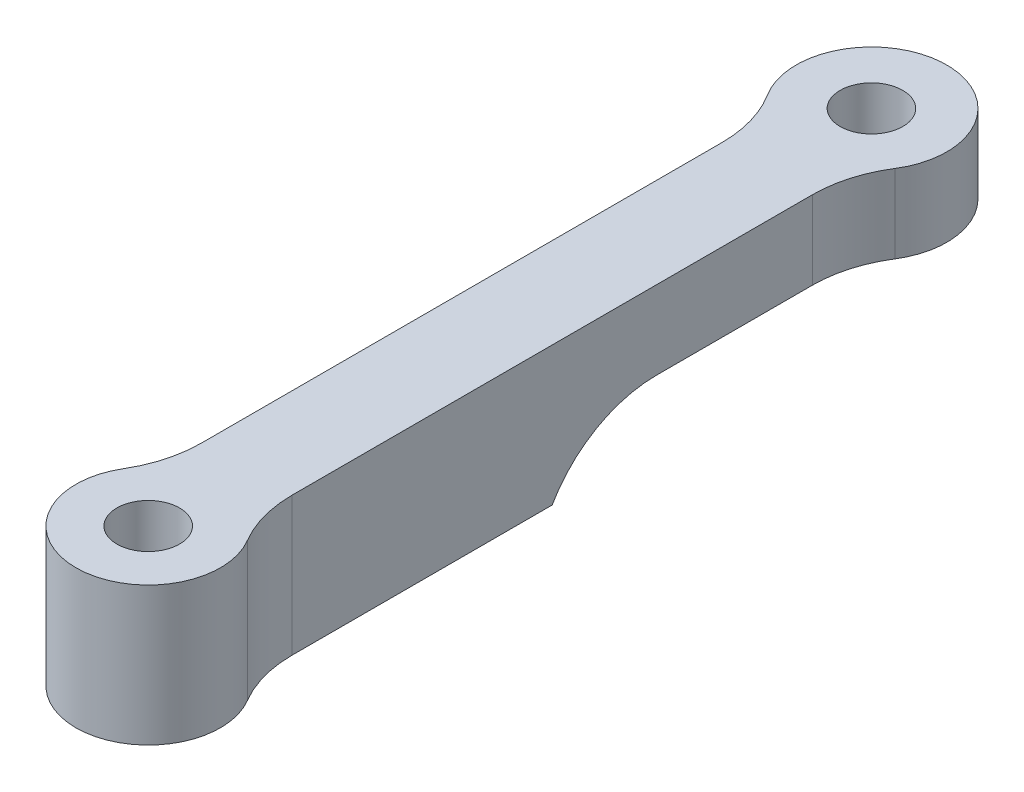
SolidWorks part; units mm, degrees
material "ABS"
ref_plane "Front Plane" through (0, 0, 0) normal (0, 0, 1) x (1, 0, 0)
ref_plane "Top Plane" through (0, 0, 0) normal (0, 1, 0) x (1, 0, 0)
ref_plane "Right Plane" through (0, 0, 0) normal (1, 0, 0) x (0, 0, -1)
sketch "Sketch1" plane through (0, 0, 0) normal (0, 1, 0) x (1, 0, 0)
  line L1 (-3.75, 55) -> (3.75, 55)
  line L2 (-3.75, 55) -> (-3.75, 4.6837)
  line L3 (-3.75, 4.6837) -> (3.75, 4.6837)
  line L4 (3.75, 55) -> (3.75, 4.6837)
  circle A0 centre (0, 0) radius 2.6
  circle A1 centre (0, 60) radius 2.6
  circle A2 centre (0, 60) radius 6.25
  circle A3 centre (0, 0) radius 6
  dimension "D1" = 5.2
  dimension "D2" = 5.2
  dimension "D3" = 12
  dimension "D4" = 12.5
  dimension "D5" = 60
  dimension "D6" = 7.5
extrude "Boss-Extrude1" add sketch "Sketch1" along normal blind 11.5 contours A3 L4 A2 L2 | L3 A3 A0 | L3 A3 | L1 A2 A1 | L1 L4 L3 L2 region at (-2.7199, 0, -65.4398) region at (0, 0, -29.8653) region at (0, 0, -5.2155) region at (0, 0, -4.5231)
fillet "Fillet1" radius 10 4 edges at (-3.75, 5.75, -4.6837) (-3.75, 5.75, -55) (3.75, 5.75, -4.6837) (3.75, 5.75, -55)
sketch "Sketch2" plane through (0, 0, 0) normal (0, -1, 0) x (1, 0, 0)
  line L0 (-3.75, -51.3397) -> (-3.75, -8.1815) construction
  line L1 (6.25, -66.25) -> (-6.25, -66.25)
  line L2 (6.25, -66.25) -> (6.25, -29.7606)
  line L3 (6.25, -29.7606) -> (-6.25, -29.7606)
  line L4 (-6.25, -66.25) -> (-6.25, -29.7606)
  arc A2 (-5.2885, -56.6691) -> (5.2885, -56.6691) centre (0, -60) ccw construction
  point P10 (-3.75, -29.7606)
extrude "Cut-Extrude1" cut sketch "Sketch2" against normal blind 5
fillet "Fillet2" radius 10 1 edges at (0, 5, -29.7606)
